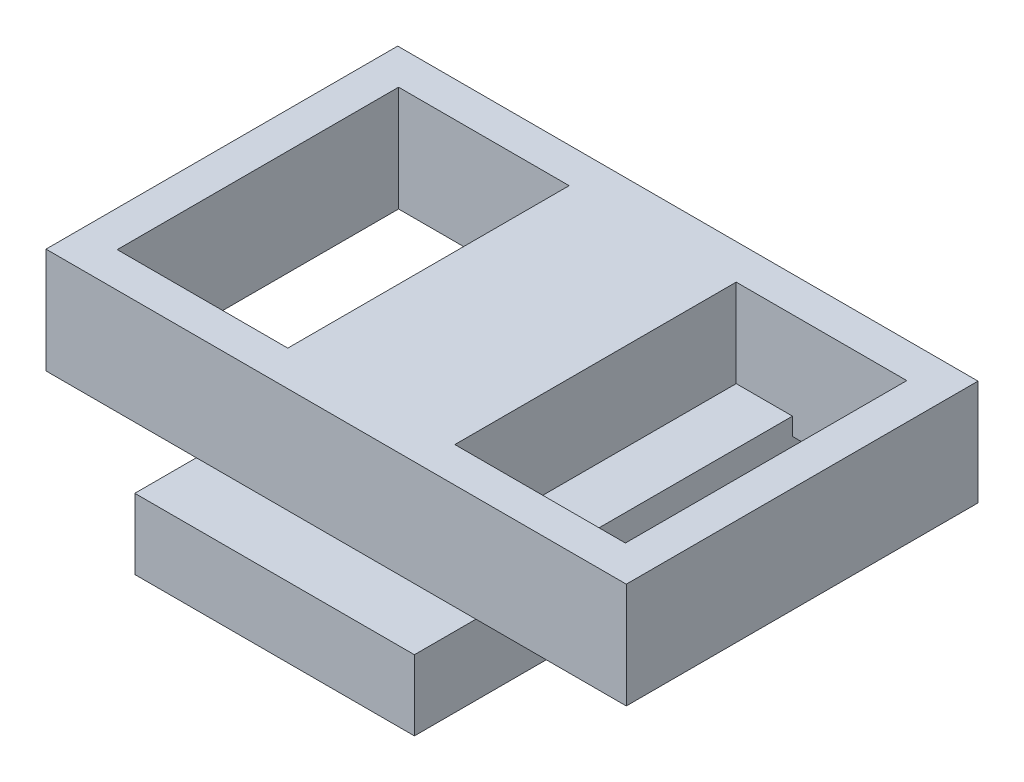
SolidWorks part; units mm, degrees
ref_plane "Płaszczyzna przednia" through (0, 0, 0) normal (0, 0, 1) x (1, 0, 0)
ref_plane "Płaszczyzna górna" through (0, 0, 0) normal (0, 1, 0) x (1, 0, 0)
ref_plane "Płaszczyzna prawa" through (0, 0, 0) normal (1, 0, 0) x (0, 0, -1)
sketch "Szkic1" plane through (0, 0, 0) normal (0, 1, 0) x (1, 0, 0)
  line L1 (16.5, -10) -> (-16.5, -10)
  line L2 (16.5, -10) -> (16.5, 10)
  line L3 (16.5, 10) -> (-16.5, 10)
  line L4 (-16.5, -10) -> (-16.5, 10)
  line L5 (16.5, -10) -> (-16.5, 10) construction
  line L6 (16.5, 10) -> (-16.5, -10) construction
  point P0 (0, 0)
  dimension "D1" = 20
  dimension "D2" = 33
extrude "Dodanie-wyciągnięcie1" add sketch "Szkic1" along normal blind 6
sketch "Szkic2" plane through (0, 6, 0) normal (0, 1, 0) x (1, 0, 0)
  line L0 (0, 10) -> (0, -10) construction
  line L1 (-14.45, 8) -> (-4.75, 8)
  line L2 (-14.45, 8) -> (-14.45, -8)
  line L3 (-14.45, -8) -> (-4.75, -8)
  line L4 (-4.75, 8) -> (-4.75, -8)
  line L5 (-14.45, 8) -> (-4.75, -8) construction
  line L6 (-14.45, -8) -> (-4.75, 8) construction
  line L7 (16.5, 10) -> (-16.5, 10) construction
  line L8 (-16.5, -10) -> (16.5, -10) construction
  line L9 (14.45, -8) -> (4.75, -8)
  line L10 (4.75, 8) -> (4.75, -8)
  line L11 (14.45, 8) -> (4.75, 8)
  line L12 (14.45, 8) -> (14.45, -8)
  line L14 (-7.95, 8) -> (-7.95, -8)
  line L15 (7.95, 8) -> (7.95, -8)
  line L17 (-16.5, 10) -> (-16.5, -10) construction
  line L18 (16.5, -10) -> (16.5, 10) construction
  point P0 (-9.6, 0)
  dimension "D1" = 16
  dimension "D2" = 9.7
  dimension "D3" = 9.5
  dimension "D4" = 6.5
extrude "Wytnij-wyciągnięcie1" cut sketch "Szkic2" against normal blind 5 contours L1 L4 L3 L2 | L11 L10 L9 L12
extrude "Wytnij-wyciągnięcie2" cut sketch "Szkic2<4>" against normal through all contours L14 L1 L2 L3 | L11 L15 L9 L12 region at (-11.2, 6, 0) region at (11.2, 6, 0)
sketch "Szkic2<4>" plane through (0, 6, 0) normal (0, 1, 0) x (1, 0, 0) same geometry as "Szkic2"
sketch "Szkic3" plane through (0, 0, 0) normal (0, -1, 0) x (1, 0, 0)
  line L0 (-7.95, -8) -> (-7.95, 8) construction
  line L1 (7.95, -13.5) -> (-7.95, -13.5)
  line L2 (7.95, -13.5) -> (7.95, 13.5)
  line L3 (7.95, 13.5) -> (-7.95, 13.5)
  line L4 (-7.95, -13.5) -> (-7.95, 13.5)
  line L5 (7.95, -13.5) -> (-7.95, 13.5) construction
  line L6 (7.95, 13.5) -> (-7.95, -13.5) construction
  point P1 (0, 0)
  dimension "D1" = 27
extrude "Dodanie-wyciągnięcie2" add sketch "Szkic3" along normal blind 4
sketch "Szkic4" plane through (0, -4, 0) normal (0, -1, 0) x (1, 0, 0)
  line L1 (5.25, -11.75) -> (-5.25, -11.75)
  line L2 (5.25, -11.75) -> (5.25, 11.75)
  line L3 (5.25, 11.75) -> (-5.25, 11.75)
  line L4 (-5.25, -11.75) -> (-5.25, 11.75)
  line L5 (5.25, -11.75) -> (-5.25, 11.75) construction
  line L6 (5.25, 11.75) -> (-5.25, -11.75) construction
  point P0 (0, 0)
  dimension "D1" = 10.5
  dimension "D2" = 23.5
extrude "Wytnij-wyciągnięcie3" cut sketch "Szkic4" against normal blind 2.5
